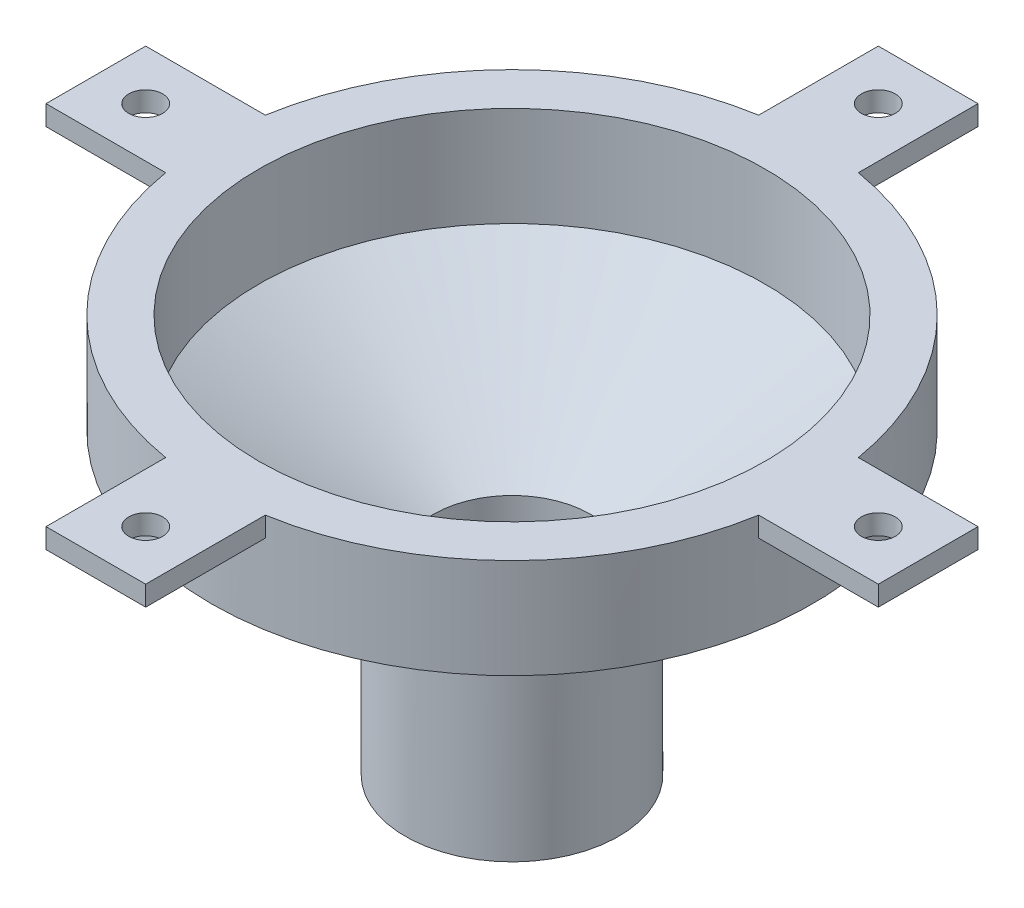
SolidWorks part; units mm, degrees
ref_plane "Front Plane" through (0, 0, 0) normal (0, 0, 1) x (1, 0, 0)
ref_plane "Top Plane" through (0, 0, 0) normal (0, 1, 0) x (1, 0, 0)
ref_plane "Right Plane" through (0, 0, 0) normal (1, 0, 0) x (0, 0, -1)
sketch "Sketch1" plane through (0, 0, 0) normal (0, 0, 1) x (1, 0, 0)
  line L0 (0, 0) -> (0, 47.7) construction
  line L1 (0, 47.7) -> (3.25, 47.7) construction
  line L2 (3.25, 47.7) -> (4.8, 47.7)
  line L3 (4.8, 47.7) -> (5.2, 43.2178)
  line L4 (5.2, 43.2178) -> (4.8, 42.5333)
  line L5 (4.8, 42.5333) -> (5.2, 38.0511)
  line L6 (5.2, 38.0511) -> (4.8, 37.3667)
  line L7 (4.8, 37.3667) -> (5.2, 32.8845)
  line L8 (5.2, 32.8845) -> (4.8, 32.2)
  line L9 (4.8, 32.2) -> (5.25, 26.2)
  line L10 (5.5, 0) -> (5.5, 18)
  line L11 (5.5, 18) -> (3.25, 19.7)
  line L12 (5.25, 26.2) -> (5.25, 22.2)
  line L13 (5.25, 22.2) -> (10.6, 22.2)
  line L14 (10.6, 22.2) -> (10.6, 15)
  line L15 (10.6, 15) -> (8.3, 15)
  line L16 (8.3, 15) -> (8.3, 0)
  line L17 (8.3, 0) -> (5.5, 0)
  line L18 (3.25, 19.7) -> (3.25, 47.7)
  dimension "D1" = 6.5
  dimension "D2" = 9.6
  dimension "D3" = 10.4
  dimension "D4" = 47.7
  dimension "D5" = 4.5
  dimension "D6" = 25.5
  dimension "D7" = 21.2
  dimension "D8" = 7.2
  dimension "D9" = 4
  dimension "D10" = 10.5
  dimension "D11" = 6
  dimension "D12" = 16.6
  dimension "D13" = 11
  dimension "D14" = 28
  dimension "D15" = 18
revolve "Revolve1" add sketch "Sketch1" angle 360 about L0
sketch "Sketch5" plane through (0, 22.2, 0) normal (0, 1, 0) x (1, 0, 0)
  line L0 (-5.3, 9.1799) -> (5.3, 9.1799)
  line L1 (5.3, 9.1799) -> (10.6, 0)
  line L2 (10.6, 0) -> (8.3, 0) construction
  line L3 (10.6, 0) -> (5.3, -9.1799)
  line L4 (5.3, -9.1799) -> (-5.3, -9.1799)
  line L5 (-5.3, -9.1799) -> (-10.6, 0)
  line L6 (-10.6, 0) -> (-5.3, 9.1799)
  circle A0 centre (0, 0) radius 10.6 construction
extrude "Cut-Extrude1" cut sketch "Sketch5" against normal up to surface (7.2 mm away) flip side to cut up to face at (0, 15, -10.6)
sketch "Sketch4" plane through (0, 0, 0) normal (0, 0, 1) x (1, 0, 0)
  line L0 (6.9, 0) -> (8.3, 1.4)
  line L1 (8.3, 0) -> (5.5, 0) construction
  line L2 (8.3, 15) -> (8.3, 0) construction
  line L3 (8.3, 1.4) -> (8.3, 0)
  line L4 (8.3, 0) -> (6.9, 0)
  line L5 (0, 0) -> (0, 15) construction
  line L6 (0, 0) -> (0, 47.7) construction
  line L7 (-8.3, 15) -> (8.3, 15) construction
  line L8 (0, 15) -> (8.3, 15) construction
  line L10 (8.3, 15) -> (10.6, 15.8371)
  line L11 (10.6, 22.2) -> (10.6, 15) construction
  line L12 (10.6, 15.8371) -> (10.6, 15)
  line L13 (10.6, 15) -> (8.3, 15)
  line L14 (8.3, 15) -> (8.3, 22.2) construction
  line L15 (5.25, 22.2) -> (10.6, 22.2) construction
  line L16 (8.3, 22.2) -> (10.6, 21.3629)
  line L17 (10.6, 21.3629) -> (10.6, 22.2)
  line L18 (10.6, 22.2) -> (8.3, 22.2)
  dimension "D1" = 45
  dimension "D2" = 20
revolve "Cut-Revolve1" cut sketch "Sketch4" angle 360 about L5
sketch "Sketch10" plane through (0, 0, 0) normal (0, -1, 0) x (1, 0, 0)
  circle A0 centre (0, 0) radius 10.705
  circle A3 centre (0, 0) radius 6.9 construction
  circle A4 centre (0, 0) radius 6.9
  dimension "D1" = 21.41
extrude "Boss-Extrude1" add sketch "Sketch10" against normal up to surface (15.8753 mm away) up to face at (0, 15.8371, 0)
sketch "Sketch11" plane through (0, 0, 0) normal (0, -1, 0) x (1, 0, 0)
  circle A0 centre (0, 0) radius 7.874
  circle A1 centre (0, 0) radius 5.5 construction
  circle A2 centre (0, 0) radius 5.5
  dimension "D1" = 15.748
extrude "Cut-Extrude2" cut sketch "Sketch11" against normal up to surface (16.2063 mm away) up to face at (0, 18, -5.5)
sketch "Sketch22" plane through (0, 0, 0) normal (0, -1, 0) x (1, 0, 0)
  circle A0 centre (0, 0) radius 7.874 construction
  circle A1 centre (0, 0) radius 10.705
  circle A2 centre (0, 0) radius 10.705
  circle A3 centre (0, 0) radius 7.874
  dimension "D1" = 0
extrude "Boss-Extrude7" add sketch "Sketch22" along normal blind 3
sketch "Sketch12" plane through (0, 22.2, 0) normal (0, 1, 0) x (1, 0, 0)
  line L0 (-7.6094, 13.1799) -> (-15.2188, 0)
  line L1 (-15.2188, 0) -> (-7.6094, -13.1799)
  line L2 (-7.6094, -13.1799) -> (7.6094, -13.1799)
  line L3 (7.6094, -13.1799) -> (15.2188, 0)
  line L4 (15.2188, 0) -> (7.6094, 13.1799)
  line L5 (7.6094, 13.1799) -> (-7.6094, 13.1799)
  line L6 (-5.3, 9.1799) -> (-10.6, 0)
  line L7 (-10.6, 0) -> (-5.3, -9.1799)
  line L8 (-5.3, -9.1799) -> (5.3, -9.1799)
  line L9 (5.3, -9.1799) -> (10.6, 0)
  line L10 (10.6, 0) -> (5.3, 9.1799)
  line L11 (5.3, 9.1799) -> (-5.3, 9.1799)
  line L12 (-5.3, 9.1799) -> (-10.6, 0) construction
  line L13 (-10.6, 0) -> (-5.3, -9.1799) construction
  line L14 (-5.3, -9.1799) -> (5.3, -9.1799) construction
  line L15 (5.3, -9.1799) -> (10.6, 0) construction
  line L16 (10.6, 0) -> (5.3, 9.1799) construction
  line L17 (5.3, 9.1799) -> (-5.3, 9.1799) construction
  circle A0 centre (0, 0) radius 8.3 construction
  circle A1 centre (0, 0) radius 8.3
  dimension "D1" = 0
  dimension "D2" = 4
extrude "Boss-Extrude3" add sketch "Sketch12" against normal up to surface (4.6818 mm away) up to face at (0, 15.8371, 0)
sketch "Sketch13" plane through (0, 47.7, 0) normal (0, 1, 0) x (1, 0, 0)
  circle A0 centre (0, 0) radius 3.45
  circle A1 centre (0, 0) radius 3.25 construction
  dimension "D1" = 0.2
extrude "Cut-Extrude3" cut sketch "Sketch13" against normal up to surface (28.1511 mm away)
sketch "Sketch14" plane through (0, 47.7, 0) normal (0, 1, 0) x (1, 0, 0)
  circle A0 centre (0, 0) radius 23.9795
extrude "Cut-Extrude5" cut sketch "Sketch14" against normal blind 32
sketch "Sketch20" plane through (0, 0, 0) normal (1, 0, 0) x (0, 0, -1)
  line L0 (10.705, 15.7) -> (30.1625, 26.9338)
  line L1 (30.1625, 26.9338) -> (27.3315, 26.9338)
  line L2 (27.3315, 26.9338) -> (7.874, 15.7)
  line L3 (7.874, 15.7) -> (10.705, 15.7)
  line L4 (0, 0) -> (0, 44.2564) construction
  dimension "D1" = 30.1625
  dimension "D2" = 150
ref_axis "Axis1" through (0, 30.702, 0) along (0, -1, 0)
revolve "Revolve2" add sketch "Sketch20" angle 360 about axis through (0, 30.702, 0) along (0, -1, 0)
sketch "Sketch17" plane through (0, 26.9338, 0) normal (0, 1, 0) x (1, 0, 0)
  circle A0 centre (0, 0) radius 25.4
  circle A2 centre (0, 0) radius 30.1625
  dimension "D2" = 50.8
  dimension "D1" = 60.325
extrude "Boss-Extrude5" add sketch "Sketch17" along normal blind 10
sketch "Sketch18" plane through (0, 36.9338, 0) normal (0, 1, 0) x (1, 0, 0)
  line L0 (-30.1625, 0) -> (0, 0) construction
  line L1 (0, 0) -> (30.1625, 0) construction
  line L2 (0, -30.1625) -> (0, 0) construction
  line L3 (0, 0) -> (0, 30.1625) construction
  line L4 (-29.7452, 5) -> (-29.7452, -5)
  line L5 (-29.7452, 5) -> (-41.7452, 5)
  line L6 (-29.7452, -5) -> (-41.7452, -5)
  line L7 (-41.7452, 5) -> (-41.7452, -5)
  line L8 (29.7452, 5) -> (29.7452, -5)
  line L9 (29.7452, 5) -> (41.7452, 5)
  line L10 (29.7452, -5) -> (41.7452, -5)
  line L11 (41.7452, 5) -> (41.7452, -5)
  line L12 (-5, -29.7452) -> (5, -29.7452)
  line L13 (-5, -29.7452) -> (-5, -41.7452)
  line L14 (5, -29.7452) -> (5, -41.7452)
  line L15 (-5, -41.7452) -> (5, -41.7452)
  line L16 (-5, 29.7452) -> (5, 29.7452)
  line L17 (-5, 29.7452) -> (-5, 41.7452)
  line L18 (5, 29.7452) -> (5, 41.7452)
  line L19 (-5, 41.7452) -> (5, 41.7452)
  line L20 (29.7452, 0) -> (36.7452, 0) construction
  line L21 (0, -36.7452) -> (0, -29.7452) construction
  line L22 (-36.7452, 0) -> (-29.7452, 0) construction
  line L23 (0, 29.7452) -> (0, 36.7452) construction
  arc A0 (29.7452, 5) -> (29.7452, -5) centre (0, 0) cw
  circle A1 centre (0, 0) radius 30.1625 construction
  arc A2 (-29.7452, 5) -> (-29.7452, -5) centre (0, 0) ccw
  arc A3 (-5, -29.7452) -> (5, -29.7452) centre (0, 0) ccw
  arc A4 (-5, 29.7452) -> (5, 29.7452) centre (0, 0) cw
  circle A5 centre (0, 36.7452) radius 1.7
  circle A6 centre (-36.7452, 0) radius 1.7
  circle A7 centre (0, -36.7452) radius 1.7
  circle A8 centre (36.7452, 0) radius 1.7
  circle M5 centre (0, 0) radius 30.1625
  dimension "D1" = 10
  dimension "D4" = 3.4
  dimension "D2" = 12
  dimension "D3" = 7
extrude "Boss-Extrude6" add sketch "Sketch18" against normal blind 2 contours L5 L7 L6 M5 | L13 L15 L14 M5 | L11 L9 L10 M5 | L19 L17 L18 M5 region at (-30.3187, 36.9338, 0) region at (-4.8438, 36.9338, -35.7452) region at (0, 36.9338, 30.3187) region at (35.7452, 36.9338, -4.8438)
